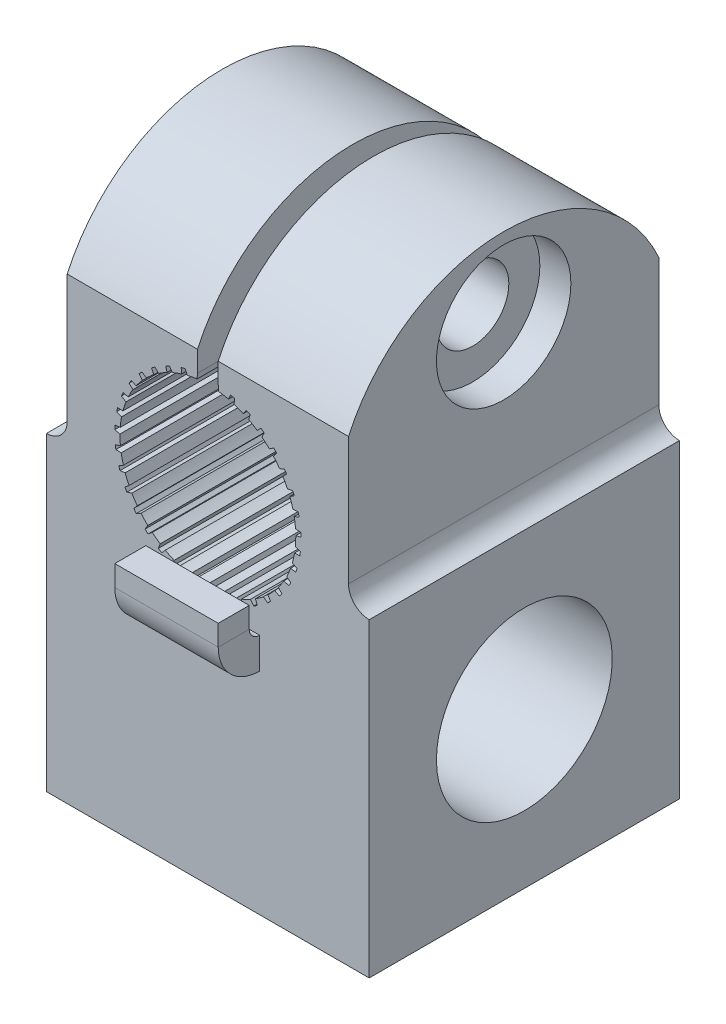
SolidWorks part; units mm, degrees
ref_plane "Piano frontale" through (0, 0, 0) normal (0, 0, 1) x (1, 0, 0)
ref_plane "Piano superiore" through (0, 0, 0) normal (0, 1, 0) x (1, 0, 0)
ref_plane "Piano destro" through (0, 0, 0) normal (1, 0, 0) x (0, 0, -1)
sketch "Schizzo1" plane through (0, 0, 0) normal (0, 0, 1) x (1, 0, 0)
  line L0 (-7.8, 0) -> (-7.8, 15)
  line L1 (-7.8, 15) -> (-6.8, 15)
  line L2 (-6.8, 15) -> (-6.8, 27)
  line L3 (-6.8, 27) -> (-0.5, 27)
  line L4 (-0.5, 27) -> (-0.5, 21.1721)
  line L5 (0.5, 27) -> (0.5, 21.1721)
  line L6 (0.5, 27) -> (6.8, 27)
  line L7 (6.8, 27) -> (6.8, 15)
  line L8 (6.8, 15) -> (7.8, 15)
  line L9 (7.8, 15) -> (7.8, 0)
  line L10 (7.8, 0) -> (-7.8, 0)
  line L11 (0, 0) -> (0, 37.7654) construction
  line L12 (-7.8, 7.5) -> (7.8, 7.5) construction
  line L13 (-0.5, 21.1721) -> (-0.5211, 20.9179)
  line L14 (-0.9911, 20.8328) -> (-1.1, 21.0635)
  line L15 (-0.2373, 20.9434) -> (-0.3032, 21.1898) [skipped]
  line L16 (-0.9911, 20.8328) -> (-0.5973, 19.9982) construction
  line L17 (-0.5973, 19.9982) -> (-0.5211, 20.9179) construction
  line L18 (0.3066, 21.1895) -> (0.2405, 20.9432) [skipped]
  line L19 (0.5242, 20.9175) -> (0.5034, 21.1718)
  line L20 (1.1033, 21.0627) -> (0.9942, 20.8321)
  line L21 (1.2689, 20.7562) -> (1.2937, 21.01)
  line L22 (1.8645, 20.7955) -> (1.7161, 20.5881)
  line L23 (1.9727, 20.4644) -> (2.0425, 20.7097)
  line L24 (2.5659, 20.3968) -> (2.3827, 20.2192)
  line L25 (2.6132, 20.0517) -> (2.7257, 20.2806)
  line L26 (3.1847, 19.8792) -> (2.9728, 19.7372)
  line L27 (3.1697, 19.5312) -> (3.3212, 19.7364)
  line L28 (3.7012, 19.2595) -> (3.4674, 19.1576)
  line L29 (3.6243, 18.9197) -> (3.81, 19.0946)
  line L30 (4.0987, 18.5575) -> (3.8505, 18.499)
  line L31 (3.9624, 18.2369) -> (4.1763, 18.3758)
  line L32 (4.3645, 17.7958) -> (4.1098, 17.7825)
  line L33 (4.1731, 17.5047) -> (4.4084, 17.6031)
  line L34 (4.4901, 16.9989) -> (4.2371, 17.0313)
  line L35 (4.2497, 16.7467) -> (4.4989, 16.8015)
  line L36 (4.4713, 16.1923) -> (4.2281, 16.2694)
  line L37 (4.1898, 15.9871) -> (4.4447, 15.9965)
  line L38 (4.3088, 15.4021) -> (4.0833, 15.5214)
  line L39 (3.9952, 15.2504) -> (4.2476, 15.2142)
  line L40 (4.0078, 14.6536) -> (3.8072, 14.8112)
  line L41 (3.6721, 14.5604) -> (3.9141, 14.4796)
  line L42 (3.578, 13.9709) -> (3.4088, 14.1618)
  line L43 (3.2311, 13.9391) -> (3.4547, 13.8164)
  line L44 (3.0332, 13.3759) -> (2.9008, 13.5939)
  line L45 (2.6861, 13.4065) -> (2.8843, 13.2459)
  line L46 (2.3909, 12.8877) -> (2.2996, 13.1258)
  line L47 (2.0549, 12.9798) -> (2.2212, 12.7864)
  line L48 (1.6717, 12.522) -> (1.6244, 12.7727)
  line L49 (1.3576, 12.6727) -> (1.4867, 12.4527)
  line L50 (0.8989, 12.2907) -> (0.8971, 12.5457)
  line L51 (0.6167, 12.495) -> (0.7044, 12.2555)
  line L52 (0.0971, 12.201) -> (0.1409, 12.4523)
  line L53 (-0.1441, 12.4524) -> (-0.1005, 12.2011)
  line L54 (-0.7078, 12.256) -> (-0.6198, 12.4954)
  line L55 (-0.9002, 12.5464) -> (-0.9022, 12.2914)
  line L56 (-1.4899, 12.4538) -> (-1.3606, 12.6737)
  line L57 (-1.6274, 12.7739) -> (-1.6749, 12.5233)
  line L58 (-2.2241, 12.7881) -> (-2.0577, 12.9813)
  line L59 (-2.3022, 13.1276) -> (-2.3937, 12.8895)
  line L60 (-2.8869, 13.2481) -> (-2.6886, 13.4085)
  line L61 (-2.9031, 13.5961) -> (-3.0357, 13.3781)
  line L62 (-3.4569, 13.819) -> (-3.2331, 13.9415)
  line L63 (-3.4107, 14.1643) -> (-3.58, 13.9736)
  line L64 (-3.9157, 14.4826) -> (-3.6737, 14.5631)
  line L65 (-3.8086, 14.8141) -> (-4.0093, 14.6566)
  line L66 (-4.2487, 15.2174) -> (-3.9962, 15.2534)
  line L67 (-4.0842, 15.5244) -> (-4.3097, 15.4053)
  line L68 (-4.4452, 15.9999) -> (-4.1903, 15.9902)
  line L69 (-4.2285, 16.2726) -> (-4.4717, 16.1957)
  line L70 (-4.4988, 16.8048) -> (-4.2497, 16.7498)
  line L71 (-4.2368, 17.0345) -> (-4.4898, 17.0022)
  line L72 (-4.4078, 17.6064) -> (-4.1725, 17.5079)
  line L73 (-4.109, 17.7856) -> (-4.3637, 17.7991)
  line L74 (-4.1751, 18.3789) -> (-3.9612, 18.2399)
  line L75 (-3.8491, 18.5019) -> (-4.0973, 18.5606)
  line L76 (-3.8082, 19.0974) -> (-3.6226, 18.9225)
  line L77 (-3.4655, 19.1602) -> (-3.6993, 19.2623)
  line L78 (-3.3189, 19.7389) -> (-3.1675, 19.5336)
  line L79 (-2.9706, 19.7395) -> (-3.1823, 19.8816)
  line L80 (-2.723, 20.2827) -> (-2.6107, 20.0536)
  line L81 (-2.3801, 20.221) -> (-2.5631, 20.3987)
  line L82 (-2.0395, 20.7113) -> (-1.9699, 20.4659)
  line L83 (-1.7132, 20.5894) -> (-1.8615, 20.7969)
  line L84 (-1.2905, 21.011) -> (-1.2658, 20.7571)
  line L85 (0.5, 21.1721) -> (0.5034, 21.1718)
  arc A0 (0.2405, 20.9432) -> (-0.2373, 20.9434) centre (0, 16.7) ccw [skipped]
  arc A1 (-0.5211, 20.9179) -> (-0.9911, 20.8328) centre (0, 16.7) ccw
  arc A2 (0.9942, 20.8321) -> (0.5242, 20.9175) centre (0, 16.7) ccw
  arc A3 (1.7161, 20.5881) -> (1.2689, 20.7562) centre (0, 16.7) ccw
  arc A4 (2.3827, 20.2192) -> (1.9727, 20.4644) centre (0, 16.7) ccw
  arc A5 (2.9728, 19.7372) -> (2.6132, 20.0517) centre (0, 16.7) ccw
  arc A6 (3.4674, 19.1576) -> (3.1697, 19.5312) centre (0, 16.7) ccw
  arc A7 (3.8505, 18.499) -> (3.6243, 18.9197) centre (0, 16.7) ccw
  arc A8 (4.1098, 17.7825) -> (3.9624, 18.2369) centre (0, 16.7) ccw
  arc A9 (4.2371, 17.0313) -> (4.1731, 17.5047) centre (0, 16.7) ccw
  arc A10 (4.2281, 16.2694) -> (4.2497, 16.7467) centre (0, 16.7) ccw
  arc A11 (4.0833, 15.5214) -> (4.1898, 15.9871) centre (0, 16.7) ccw
  arc A12 (3.8072, 14.8112) -> (3.9952, 15.2504) centre (0, 16.7) ccw
  arc A13 (3.4088, 14.1618) -> (3.6721, 14.5604) centre (0, 16.7) ccw
  arc A14 (2.9008, 13.5939) -> (3.2311, 13.9391) centre (0, 16.7) ccw
  arc A15 (2.2996, 13.1258) -> (2.6861, 13.4065) centre (0, 16.7) ccw
  arc A16 (1.6244, 12.7727) -> (2.0549, 12.9798) centre (0, 16.7) ccw
  arc A17 (0.8971, 12.5457) -> (1.3576, 12.6727) centre (0, 16.7) ccw
  arc A18 (0.1409, 12.4523) -> (0.6167, 12.495) centre (0, 16.7) ccw
  arc A19 (-0.6198, 12.4954) -> (-0.1441, 12.4524) centre (0, 16.7) ccw
  arc A20 (-1.3606, 12.6737) -> (-0.9002, 12.5464) centre (0, 16.7) ccw
  arc A21 (-2.0577, 12.9813) -> (-1.6274, 12.7739) centre (0, 16.7) ccw
  arc A22 (-2.6886, 13.4085) -> (-2.3022, 13.1276) centre (0, 16.7) ccw
  arc A23 (-3.2331, 13.9415) -> (-2.9031, 13.5961) centre (0, 16.7) ccw
  arc A24 (-3.6737, 14.5631) -> (-3.4107, 14.1643) centre (0, 16.7) ccw
  arc A25 (-3.9962, 15.2534) -> (-3.8086, 14.8141) centre (0, 16.7) ccw
  arc A26 (-4.1903, 15.9902) -> (-4.0842, 15.5244) centre (0, 16.7) ccw
  arc A27 (-4.2497, 16.7498) -> (-4.2285, 16.2726) centre (0, 16.7) ccw
  arc A28 (-4.1725, 17.5079) -> (-4.2368, 17.0345) centre (0, 16.7) ccw
  arc A29 (-3.9612, 18.2399) -> (-4.109, 17.7856) centre (0, 16.7) ccw
  arc A30 (-3.6226, 18.9225) -> (-3.8491, 18.5019) centre (0, 16.7) ccw
  arc A31 (-3.1675, 19.5336) -> (-3.4655, 19.1602) centre (0, 16.7) ccw
  arc A32 (-2.6107, 20.0536) -> (-2.9706, 19.7395) centre (0, 16.7) ccw
  arc A33 (-1.9699, 20.4659) -> (-2.3801, 20.221) centre (0, 16.7) ccw
  arc A34 (-1.2658, 20.7571) -> (-1.7132, 20.5894) centre (0, 16.7) ccw
  arc A35 (-1.2905, 21.011) -> (-1.1, 21.0635) centre (0, 16.7) cw
  arc A38 (1.1033, 21.0627) -> (1.2937, 21.01) centre (0, 16.7) cw
  arc A39 (1.8645, 20.7955) -> (2.0425, 20.7097) centre (0, 16.7) cw
  arc A40 (2.5659, 20.3968) -> (2.7257, 20.2806) centre (0, 16.7) cw
  arc A41 (3.1847, 19.8792) -> (3.3212, 19.7364) centre (0, 16.7) cw
  arc A42 (3.7012, 19.2595) -> (3.81, 19.0946) centre (0, 16.7) cw
  arc A43 (4.0987, 18.5575) -> (4.1763, 18.3758) centre (0, 16.7) cw
  arc A44 (4.3645, 17.7958) -> (4.4084, 17.6031) centre (0, 16.7) cw
  arc A45 (4.4901, 16.9989) -> (4.4989, 16.8015) centre (0, 16.7) cw
  arc A46 (4.4713, 16.1923) -> (4.4447, 15.9965) centre (0, 16.7) cw
  arc A47 (4.3088, 15.4021) -> (4.2476, 15.2142) centre (0, 16.7) cw
  arc A48 (4.0078, 14.6536) -> (3.9141, 14.4796) centre (0, 16.7) cw
  arc A49 (3.578, 13.9709) -> (3.4547, 13.8164) centre (0, 16.7) cw
  arc A50 (3.0332, 13.3759) -> (2.8843, 13.2459) centre (0, 16.7) cw
  arc A51 (2.3909, 12.8877) -> (2.2212, 12.7864) centre (0, 16.7) cw
  arc A52 (1.6717, 12.522) -> (1.4867, 12.4527) centre (0, 16.7) cw
  arc A53 (0.8989, 12.2907) -> (0.7044, 12.2555) centre (0, 16.7) cw
  arc A54 (0.0971, 12.201) -> (-0.1005, 12.2011) centre (0, 16.7) cw
  arc A55 (-0.7078, 12.256) -> (-0.9022, 12.2914) centre (0, 16.7) cw
  arc A56 (-1.4899, 12.4538) -> (-1.6749, 12.5233) centre (0, 16.7) cw
  arc A57 (-2.2241, 12.7881) -> (-2.3937, 12.8895) centre (0, 16.7) cw
  arc A58 (-2.8869, 13.2481) -> (-3.0357, 13.3781) centre (0, 16.7) cw
  arc A59 (-3.4569, 13.819) -> (-3.58, 13.9736) centre (0, 16.7) cw
  arc A60 (-3.9157, 14.4826) -> (-4.0093, 14.6566) centre (0, 16.7) cw
  arc A61 (-4.2487, 15.2174) -> (-4.3097, 15.4053) centre (0, 16.7) cw
  circle A62 centre (0, 16.7) radius 4.25 construction
  circle A63 centre (0, 16.7) radius 4.5 construction
  arc A64 (-4.4452, 15.9999) -> (-4.4717, 16.1957) centre (0, 16.7) cw
  arc A65 (-4.4988, 16.8048) -> (-4.4898, 17.0022) centre (0, 16.7) cw
  arc A66 (-4.4078, 17.6064) -> (-4.3637, 17.7991) centre (0, 16.7) cw
  arc A67 (-4.1751, 18.3789) -> (-4.0973, 18.5606) centre (0, 16.7) cw
  arc A68 (-3.8082, 19.0974) -> (-3.6993, 19.2623) centre (0, 16.7) cw
  arc A69 (-3.3189, 19.7389) -> (-3.1823, 19.8816) centre (0, 16.7) cw
  arc A70 (-2.723, 20.2827) -> (-2.5631, 20.3987) centre (0, 16.7) cw
  arc A71 (-2.0395, 20.7113) -> (-1.8615, 20.7969) centre (0, 16.7) cw
  arc A72 (-0.5, 21.1721) -> (-0.3032, 21.1898) centre (0, 16.7) cw [skipped]
  arc A73 (0.3066, 21.1895) -> (0.5034, 21.1718) centre (0, 16.7) cw [skipped]
  point P164 (0, 16.7)
  point P232 (0, 16.7)
  dimension "D3" = 8.5
  dimension "D4" = 9
  dimension "D5" = 12
  dimension "D8" = 9.2
  dimension "D9" = 0.6
  dimension "D11" = 35
  dimension "D1" = 15
  dimension "D2" = 1
  dimension "D6" = 15.6
  dimension "D7" = 1
  dimension "D10" = 30
  dimension "D12" = 35
extrude "Main body" add sketch "Schizzo1" along normal mid plane 15 contours L14 A35 L84 A34 L83 A71 L82 A33 L81 A70 L80 A32 L79 A69 L78 A31 L77 A68 L76 A30 L75 A67 L74 A29 L73 A66 L72 A28 L71 A65 L70 A27 L69 A64 L68 A26 L67 A61 L66 A25 L65 A60 L64 A24 L63 A59 L62 A23 L61 A58 L60 A22 L59 A57 L58 A21 L57 A56 L56 A20 L55 A55 L54 A19 L53 A54 L52 A18 L51 A53 L50 A17 L49 A52 L48 A16 L47 A51 L46 A15 L45 A50 L44 A14 L43 A49 L42 A13 L41 A48 L40 A12 L39 A47 L38 A11 L37 A46 L36 A10 L35 A45 L34 A9 L33 A44 L32 A8 L31 A43 L30 A7 L29 A42 L28 A6 L27 A41 L26 A5 L25 A40 L24 A4 L23 A39 L22 A3 L21 A38 L20 A2 L19 L85 L5 L6 L7 L8 L9 L10 L0 L1 L2 L3 L4 L13 A1
sketch "Schizzo2" plane through (6.8, 0, 0) normal (1, 0, 0) x (0, 0, -1)
  line L0 (-7.5, 27) -> (7.5, 27) construction
  line L1 (-7.5, 27) -> (7.5, 27)
  line L2 (0, 27) -> (0, 23.2) construction
  circle A0 centre (0, 23.2) radius 1.75
  dimension "D1" = 3.5
  dimension "D3" = 3.8
extrude "Screw" cut sketch "Schizzo2" against normal through all both and the other way through all contours A0
sketch "Schizzo5" plane through (6.8, 0, 0) normal (1, 0, 0) x (0, 0, -1)
  circle A0 centre (0, 23.2) radius 1.75 construction
  circle A1 centre (0, 23.2) radius 1.75
  circle A2 centre (0, 23.2) radius 3.25
  dimension "D1" = 6.5
extrude "Washer recess" cut sketch "Schizzo5" against normal blind 1.5
sketch "Schizzo6" plane through (-6.8, 0, 0) normal (-1, 0, 0) x (0, 0, 1)
  line L1 (3.25, 23.2) -> (1.625, 26.0146)
  line L2 (1.625, 26.0146) -> (-1.625, 26.0146)
  line L3 (-1.625, 26.0146) -> (-3.25, 23.2)
  line L4 (-3.25, 23.2) -> (-1.625, 20.3854)
  line L5 (-1.625, 20.3854) -> (1.625, 20.3854)
  line L6 (1.625, 20.3854) -> (3.25, 23.2)
  circle A0 centre (0, 23.2) radius 2.8146 construction
  dimension "D1" = 6.5
extrude "Nut recess" cut sketch "Schizzo6" against normal blind 2.4
sketch "Schizzo10" plane through (6.8, 0, 0) normal (1, 0, 0) x (0, 0, -1)
  line L2 (-7.5, 27) -> (-7.5, 21.1721) construction
  line L3 (-7.5, 27) -> (-7.5, 21.1721) construction
  line L4 (7.5, 27) -> (7.5, 15) construction
  line L5 (-7.5, 27) -> (7.5, 27) construction
  line L6 (-7.5, 27) -> (7.5, 27) construction
  line L7 (7.5, 22.1721) -> (7.5, 27)
  arc A0 (-7.5, 22.1721) -> (7.5, 22.1721) centre (0, 18.7605) cw
  line M4 (7.5, 15) -> (7.5, 27)
  line M5 (7.5, 27) -> (-7.5, 27)
  line M6 (-7.5, 27) -> (-7.5, 15)
  dimension "D1" = 1
extrude "Curve cut" cut sketch "Schizzo10" against normal through all contours A0 M6 M5 | A0 M5 M4 region at (6.8, 25.6717, -5.7515) region at (6.8, 25.6717, 5.7515)
sketch "Schizzo7" plane through (-7.8, 0, 0) normal (-1, 0, 0) x (0, 0, 1)
  line L0 (-7.5, 15) -> (7.5, 0) construction
  circle A0 centre (0, 7.5) radius 4.25
  dimension "D1" = 8.5
extrude "Bar hole" cut sketch "Schizzo7" against normal through all
fillet "Relief 1" radius 1 1 edges at (6.8, 15, 0)
fillet "Relief 2" radius 1 1 edges at (-6.8, 15, 0)
sketch "Schizzo8" plane through (0, 0, 7.5) normal (0, 0, 1) x (1, 0, 0)
  line L0 (0.0012, 16.7) -> (0.0012, 10.2) construction
  line L1 (-2.4988, 10.2) -> (2.5012, 10.2)
  line L2 (-2.4988, 10.2) -> (-2.4988, 11.7)
  line L3 (-2.4988, 11.7) -> (2.5012, 11.7)
  line L4 (2.5012, 11.7) -> (2.5012, 10.2)
  line L5 (-2.4988, 11.7) -> (2.5012, 10.2) construction
  circle A2 centre (0.0012, 16.7) radius 4.4988 construction
  point P0 (0.0012, 10.95)
  point P6 (0.0012, 10.2)
  dimension "D2" = 5
  dimension "D1" = 1.5
  dimension "D3" = 5
sketch "Schizzo9" plane through (0, 0, 0) normal (1, 0, 0) x (0, 0, -1)
  line L0 (-7.5, 11.7) -> (-7.5, 10.2) construction
  line L1 (-7.5, 11.7) -> (-7.5, 10.2) construction
  line L2 (-8.7512, 12.2012) -> (-8.7512, 13.2012)
  line L4 (-7.5, 21.1988) -> (-7.5, 12.2012) construction
  line L5 (-7.5, 21.1988) -> (-7.5, 12.2012) construction
  arc A0 (-7.5, 10.95) -> (-8.7512, 12.2012) centre (-7.5, 12.2012) cw
  dimension "D1" = 1
sweep "Stop Rod" add profiles "Schizzo8" path "Schizzo9"
ref_axis "Bar axis" through (7.8, 7.5, 0) along (-1, 0, 0)
ref_axis "Rod axis" through (0, 16.7, 7.5) along (0, 0, -1)
ref_axis "Rod clamp axis" through (0.5, 23.2, 0) along (1, 0, 0)
